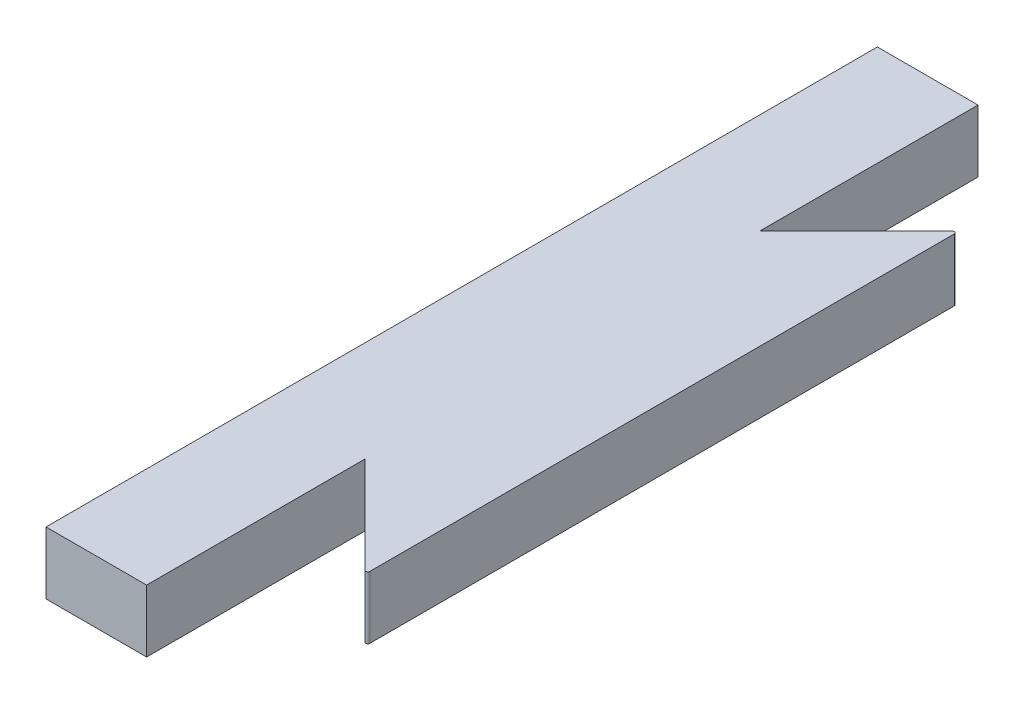
SolidWorks part; units mm, degrees
ref_plane "Alzado" through (0, 0, 0) normal (0, 0, 1) x (1, 0, 0)
ref_plane "Planta" through (0, 0, 0) normal (0, 1, 0) x (1, 0, 0)
ref_plane "Vista lateral" through (0, 0, 0) normal (1, 0, 0) x (0, 0, -1)
sketch "Croquis1" plane through (0, 0, 0) normal (0, 1, 0) x (1, 0, 0)
  line L0 (65, 9.5) -> (69.8, 14.3)
  line L1 (-65, -20) -> (65, -20)
  line L2 (-65, -20) -> (-65, 20)
  line L3 (-65, 20) -> (65, 20)
  line L4 (65, -20) -> (65, -9.5)
  line L5 (-65, -20) -> (65, 20) construction
  line L6 (-65, 20) -> (65, -20) construction
  line L7 (69.8, 14.3) -> (69.8, -14.3)
  line L8 (69.8, -14.3) -> (65, -9.5)
  line L9 (65, 9.5) -> (65, 20)
  line L10 (0, 0) -> (77.1384, 0) construction
  line L12 (10, 9.5) -> (40, 9.5)
  line L13 (10, 9.5) -> (10, 12.5)
  line L14 (10, 12.5) -> (40, 12.5)
  line L15 (40, 9.5) -> (40, 12.5)
  line L16 (10, 9.5) -> (40, 12.5) construction
  line L17 (10, 12.5) -> (40, 9.5) construction
  line L18 (10, -12.5) -> (40, -12.5)
  line L19 (10, -12.5) -> (10, -9.5)
  line L20 (10, -9.5) -> (40, -9.5)
  line L21 (40, -12.5) -> (40, -9.5)
  line L22 (10, -12.5) -> (40, -9.5) construction
  line L23 (10, -9.5) -> (40, -12.5) construction
  circle A2 centre (-50.1299, 0) radius 11
  circle A3 centre (-50.1299, 0) radius 12.5 construction
  circle A4 centre (-28.5951, 0) radius 2
  circle A5 centre (-13.5951, 0) radius 2
  circle A6 centre (50, 0) radius 2
  point P0 (0, 0)
  point P8 (69.8, 0)
  point P19 (25, 11)
  point P35 (25, -11)
  dimension "D8" = 22
  dimension "D12" = 25
  dimension "D13" = 4
  dimension "D14" = 4
  dimension "D17" = 4
  dimension "D1" = 130
  dimension "D2" = 4.8
  dimension "D3" = 45
  dimension "D5" = 28.6
  dimension "D6" = 40
  dimension "D9" = 3
  dimension "D10" = 30
  dimension "D11" = 40
  dimension "D15" = 15
  dimension "D16" = 10
  dimension "D18" = 12.5
  dimension "D19" = 12.5
extrude "Saliente-Extruir1" add sketch "Croquis1" along normal blind 3
sketch "Croquis2" plane through (0, 3, 0) normal (0, 1, 0) x (1, 0, 0)
  circle A0 centre (-50.1299, 0) radius 11
  circle A1 centre (-50.1299, 0) radius 13
  dimension "D1" = 2
extrude "Saliente-Extruir2" add sketch "Croquis2" along normal blind 4
sketch "Croquis3" plane through (0, 7, 0) normal (0, 1, 0) x (1, 0, 0)
  circle A0 centre (-50.1299, 0) radius 13
  circle A1 centre (-50.1299, 0) radius 9
  dimension "D1" = 18
extrude "Saliente-Extruir3" add sketch "Croquis3" along normal blind 2
chamfer "Chaflán1" distance 2 angle 45 1 edges at (-50.1299, 9, 13)
chamfer "Chaflán2" distance 10 angle 45 2 edges at (-65, 1.5, 20) (-65, 1.5, -20)
sketch "Croquis4" plane through (0, 3, 0) normal (0, 1, 0) x (1, 0, 0)
  line L1 (60.1587, 28.398) -> (-68.6747, 28.398)
  line L2 (60.1587, 28.398) -> (60.1587, -29.8358)
  line L3 (60.1587, -29.8358) -> (-68.6747, -29.8358)
  line L4 (-68.6747, 28.398) -> (-68.6747, -29.8358)
extrude "Cortar-Extruir1" cut sketch "Croquis4" against normal blind 10 and the other way blind 10
fillet "Redondeo1" radius 0.1 2 edges at (69.8, 1.5, -14.3) (69.8, 1.5, 14.3)
